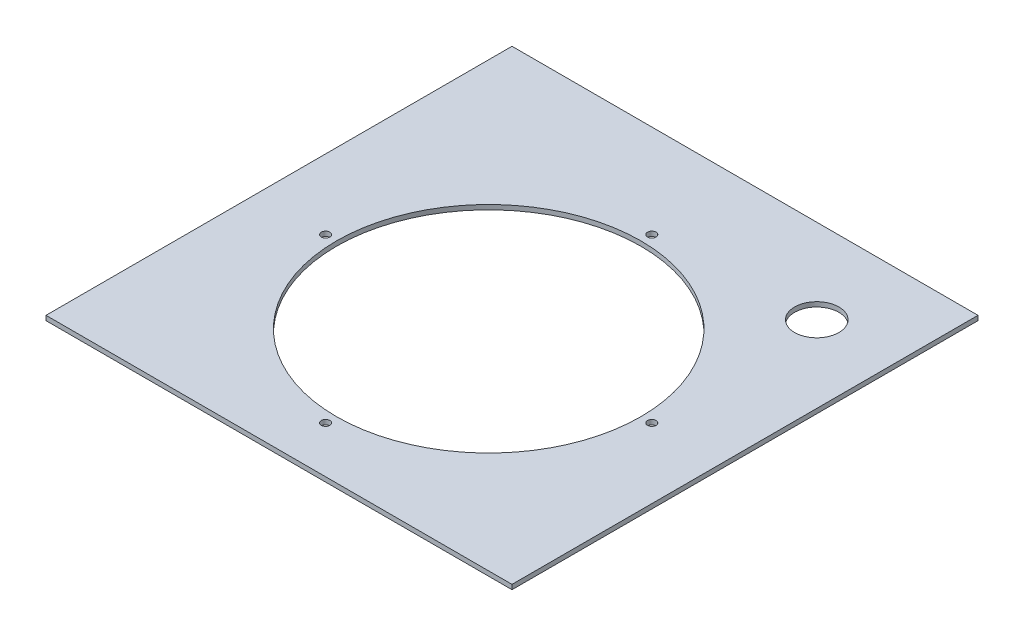
SolidWorks part; units mm, degrees
ref_plane "Front Plane" through (0, 0, 0) normal (0, 0, 1) x (1, 0, 0)
ref_plane "Top Plane" through (0, 0, 0) normal (0, 1, 0) x (1, 0, 0)
ref_plane "Right Plane" through (0, 0, 0) normal (1, 0, 0) x (0, 0, -1)
sketch "Sketch1" plane through (0, 0, 0) normal (0, 1, 0) x (1, 0, 0)
  line L1 (0, 0) -> (300, 0)
  line L2 (0, 0) -> (0, -330)
  line L3 (0, -330) -> (300, -330)
  line L4 (300, 0) -> (300, -330)
  dimension "D1" = 300
  dimension "D2" = 330
extrude "Boss-Extrude1" add sketch "Sketch1" along normal blind 3
sketch "Sketch2" plane through (0, 3, 0) normal (0, 1, 0) x (1, 0, 0)
  line L0 (300, -330) -> (300, 0) construction
  line L1 (0, -330) -> (300, -330) construction
  line L2 (150, -165) -> (300, 0) construction
  line L3 (300, 0) -> (300, -330) construction
  line L4 (0, 0) -> (300, 0) construction
  circle A0 centre (150, -165) radius 98
  circle A1 centre (250.5646, -54.379) radius 14.255
  point P5 (300, -165)
  point P8 (150, -330)
  dimension "D1" = 196
  dimension "D3" = 28.51
  dimension "D2" = 149.5
  dimension "D4" = 49.4354
  dimension "D5" = 54.379
extrude "Cut-Extrude1" cut sketch "Sketch2" against normal up to next
sketch "Sketch4" plane through (0, 3, 0) normal (0, 1, 0) x (1, 0, 0)
  line L0 (0, -330) -> (300, -330) construction
  line L1 (0, 0) -> (0, -330) construction
  line L2 (300, 0) -> (300, -330) construction
  line L3 (0, 0) -> (300, 0) construction
  circle A0 centre (150, -165) radius 105 construction
  circle A2 centre (45, -165) radius 2.75
  circle A3 centre (255, -165) radius 2.75
  circle A4 centre (150, -270) radius 2.75
  circle A5 centre (150, -60) radius 2.75
  dimension "D1" = 210
  dimension "D2" = 5.5
  dimension "D3" = 5.5
  dimension "D4" = 5.5
  dimension "D5" = 5.5
  dimension "D7" = 45
  dimension "D8" = 45
  dimension "D9" = 60
  dimension "D6" = 60
extrude "Cut-Extrude3" cut sketch "Sketch4" against normal through all contours A2 | A5 | A3 | A4
sketch "Sketch5" plane through (0, 3, 0) normal (0, 1, 0) x (1, 0, 0)
  line L0 (300, -330) -> (300, 0) construction
  line L1 (0, 0) -> (300, 0)
  line L2 (0, 0) -> (0, -300)
  line L3 (0, -300) -> (300, -300)
  line L4 (300, 0) -> (300, -300)
  line L5 (0, -330) -> (300, -330) construction
  dimension "D1" = 30
sketch "Sketch6" plane through (0, 3, 0) normal (0, 1, 0) x (1, 0, 0)
  line L0 (300, -330) -> (300, 0) construction
  line L1 (0, -330) -> (300, -330)
  line L2 (0, -330) -> (0, -300)
  line L3 (0, -300) -> (300, -300)
  line L4 (300, -330) -> (300, -300)
  dimension "D1" = 30
extrude "Cut-Extrude5" cut sketch "Sketch6" against normal through all
